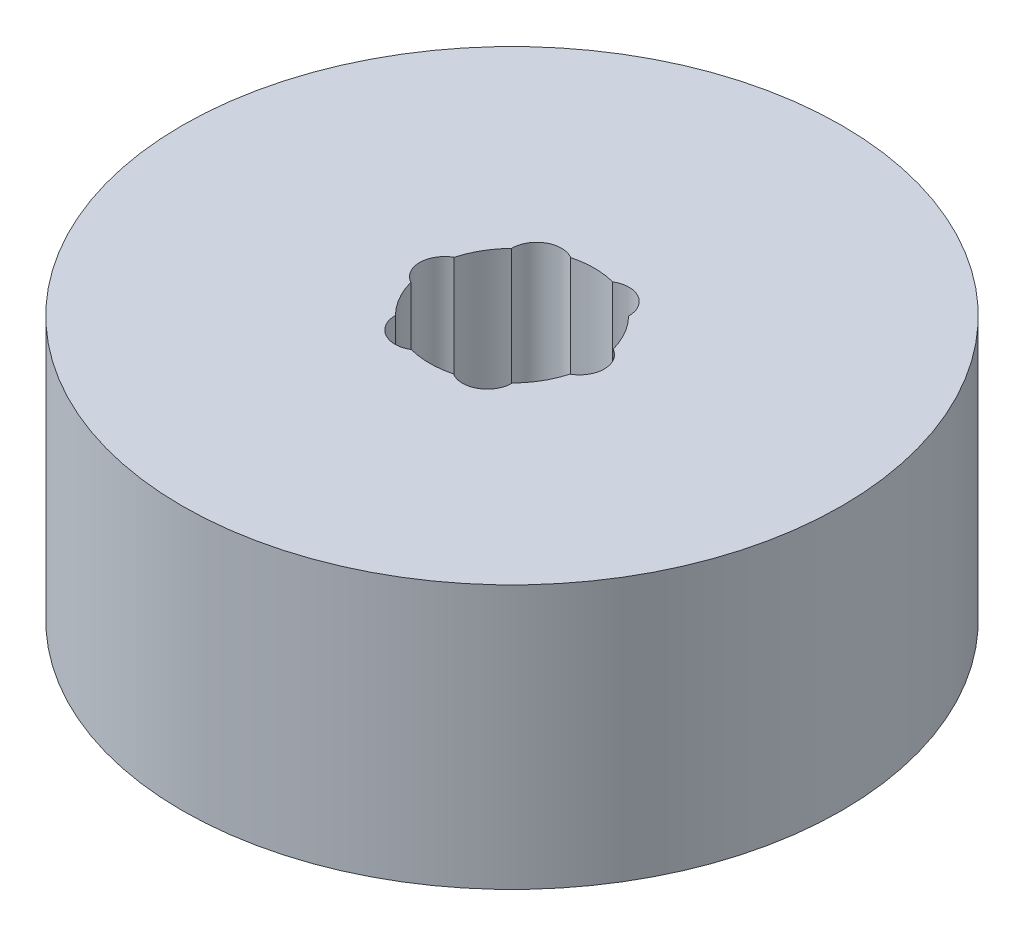
SolidWorks part; units mm, degrees
ref_plane "Front Plane" through (0, 0, 0) normal (0, 0, 1) x (1, 0, 0)
ref_plane "Top Plane" through (0, 0, 0) normal (0, 1, 0) x (1, 0, 0)
ref_plane "Right Plane" through (0, 0, 0) normal (1, 0, 0) x (0, 0, -1)
sketch "Sketch1" plane through (0, 0, 0) normal (0, 1, 0) x (1, 0, 0)
  circle A0 centre (0, 0) radius 20
  dimension "FLANGE_OD" = 40
extrude "Boss-Extrude1" add sketch "Sketch1" along normal blind 16
sketch "Sketch2" plane through (0, 0, 0) normal (0, 1, 0) x (1, 0, 0)
  circle A0 centre (0, 0) radius 5
  dimension "BORE_D" = 10
extrude "Cut-Extrude1" cut sketch "Sketch2" along normal through all
sketch "Sketch3" plane through (0, 16, 0) normal (0, 1, 0) x (1, 0, 0)
  circle A0 centre (0, 0) radius 4.0931 construction
  circle A1 centre (-4.0931, 0) radius 1.5047
  dimension "BOLT_D" = 3.0094
  dimension "BOLT_PCD" = 8.1863
extrude "Cut-Extrude2" cut sketch "Sketch3" against normal blind 12.7122
pattern_circular "CirPattern1" count 6 over 360 about axis through (0, 0, 0) along (0, 1, 0) of "Cut-Extrude2"
